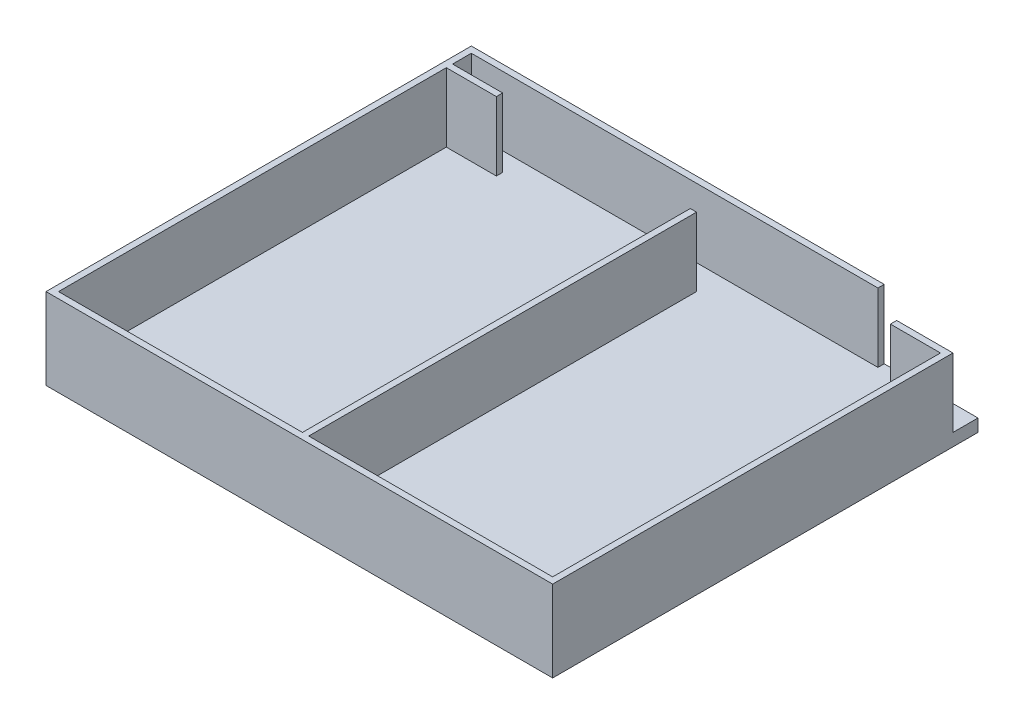
SolidWorks part; units mm, degrees
ref_plane "Front Plane" through (0, 0, 0) normal (0, 0, 1) x (1, 0, 0)
ref_plane "Top Plane" through (0, 0, 0) normal (0, 1, 0) x (1, 0, 0)
ref_plane "Right Plane" through (0, 0, 0) normal (1, 0, 0) x (0, 0, -1)
sketch "Sketch1" plane through (0, 0, 0) normal (0, 1, 0) x (1, 0, 0)
  line L0 (-0.5, 29) -> (0.5, 29)
  line L1 (42.5, 34) -> (-42.5, 34) construction
  line L2 (42.5, 34) -> (42.5, -34) construction
  line L3 (42.5, -34) -> (-42.5, -34)
  line L4 (-42.5, 34) -> (-42.5, -34) construction
  line L5 (42.5, 34) -> (-42.5, -34) construction
  line L6 (42.5, -34) -> (-42.5, 34) construction
  line L7 (-39.5, 29) -> (-0.5, 29)
  line L8 (-39.5, 29) -> (-39.5, -33)
  line L9 (-39.5, -33) -> (-0.5, -33)
  line L10 (-0.5, 29) -> (-0.5, -33)
  line L11 (0.5, 29) -> (39.5, 29)
  line L12 (0.5, 29) -> (0.5, -33)
  line L13 (0.5, -33) -> (39.5, -33)
  line L14 (39.5, 29) -> (39.5, -33)
  line L15 (-31.5, 29) -> (-31.5, 30)
  line L16 (-40.5, -34) -> (40.5, -34)
  line L17 (-40.5, -34) -> (-40.5, 34)
  line L18 (-40.5, 34) -> (40.5, 34)
  line L19 (40.5, -34) -> (40.5, 34)
  line L20 (-31.5, 30) -> (-39.5, 30)
  line L21 (-39.5, 30) -> (-39.5, 33)
  line L22 (-39.5, 33) -> (25.5, 33)
  line L23 (-8.5, 29) -> (-8.5, 30)
  line L24 (-8.5, 30) -> (8.5, 30)
  line L25 (8.5, 30) -> (8.5, 29)
  line L26 (25.5, 33) -> (25.5, 34)
  line L27 (31.5, 29) -> (31.5, 30)
  line L28 (31.5, 30) -> (40.5, 30)
  point P0 (0, 0)
  point P14 (0, 29)
  point P31 (0, 30)
  dimension "D1" = 39
  dimension "D2" = 62
  dimension "D3" = 85
  dimension "D4" = 1
  dimension "D5" = 68
  dimension "D6" = 1
  dimension "D7" = 1
  dimension "D8" = 1
  dimension "D9" = 17
  dimension "D10" = 1
  dimension "D11" = 1
  dimension "D12" = 1
  dimension "D13" = 9
  dimension "D14" = 17
  dimension "D15" = 8
extrude "Boss-Extrude1" add sketch "Sketch1" against normal blind 2 contours L28 L27 L11 L14 L13 L12 L0 L10 L9 L8 L7 L15 L20 L21 L22 L26 L18 L17 L3 L19 | L27 L28 L19 L18 L26 L22 L21 L20 L15 L7 L23 L24 L25 L11 | L10 L7 L8 L9 | L14 L11 L12 L13 | L25 L24 L23 L7 L0 L11 region at (0, 0, -29.5) region at (-20, 0, 2) region at (0, 0, -27.9424) region at (20, 0, 2) region at (2.0432, 0, -31.294)
extrude "Boss-Extrude2" add sketch "Sketch1<3>" along normal blind 11 contours L28 L27 L11 L14 L13 L12 L0 L10 L9 L8 L7 L15 L20 L21 L22 L26 L18 L17 L3 L19 region at (0, 0, -27.9424)
sketch "Sketch1<3>" plane through (0, 0, 0) normal (0, 1, 0) x (1, 0, 0) same geometry as "Sketch1"
